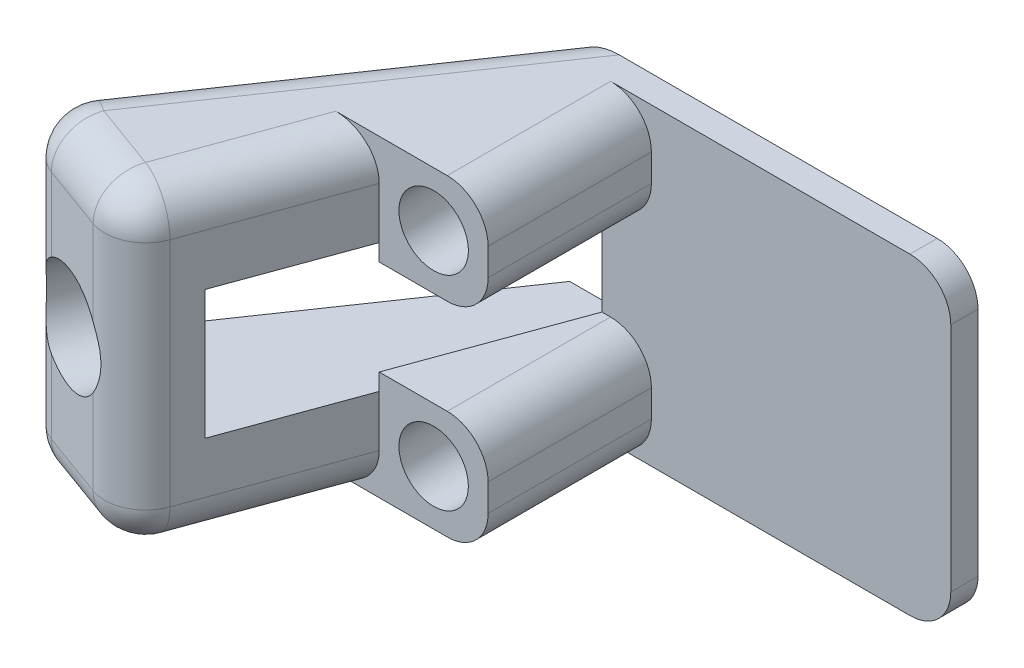
SolidWorks part; units mm, degrees
ref_plane "Alzado" through (0, 0, 0) normal (0, 0, 1) x (1, 0, 0)
ref_plane "Planta" through (0, 0, 0) normal (0, 1, 0) x (1, 0, 0)
ref_plane "Vista lateral" through (0, 0, 0) normal (1, 0, 0) x (0, 0, -1)
sketch "Croquis3" plane through (0, 0, 0) normal (0, 0, 1) x (1, 0, 0)
  line L0 (-63.169, 19.4366) -> (-33.169, 19.4366) construction
  line L1 (-63.169, 30.9366) -> (-33.169, 30.9366)
  line L2 (-63.169, 30.9366) -> (-63.169, 7.9366)
  line L3 (-63.169, 7.9366) -> (-33.169, 7.9366)
  line L4 (-33.169, 30.9366) -> (-33.169, 7.9366)
  circle A0 centre (-59.169, 26.9366) radius 2.55
  circle A1 centre (-59.169, 11.9366) radius 2.55
  dimension "D4" = 5.1
  dimension "D1" = 23
  dimension "D2" = 30
  dimension "D3" = 7.5
  dimension "D5" = 4
extrude "Saliente-Extruir2" add sketch "Croquis3" along normal blind 2
sketch "Croquis5" plane through (0, 0, 2) normal (0, 0, 1) x (1, 0, 0)
  line L0 (-63.169, 19.4366) -> (-33.169, 19.4366) construction
  line L1 (-63.169, 7.9366) -> (-55.169, 7.9366)
  line L2 (-63.169, 7.9366) -> (-63.169, 15.9366)
  line L3 (-63.169, 15.9366) -> (-55.169, 15.9366)
  line L4 (-55.169, 7.9366) -> (-55.169, 15.9366)
  line L5 (-63.169, 30.9366) -> (-63.169, 7.9366) construction
  line L6 (-33.169, 7.9366) -> (-33.169, 30.9366) construction
  line L7 (-55.169, 30.9366) -> (-55.169, 22.9366)
  line L8 (-63.169, 22.9366) -> (-55.169, 22.9366)
  line L9 (-63.169, 30.9366) -> (-63.169, 22.9366)
  line L10 (-63.169, 30.9366) -> (-55.169, 30.9366)
  circle A0 centre (-59.169, 11.9366) radius 2.55
  circle A1 centre (-59.169, 26.9366) radius 2.55
  circle A2 centre (-59.169, 11.9366) radius 2.55 construction
  dimension "D1" = 8
  dimension "D2" = 8
extrude "Saliente-Extruir3" add sketch "Croquis5" along normal blind 12
sketch "Croquis6" plane through (0, 30.9366, 0) normal (0, 1, 0) x (1, 0, 0)
  line L0 (-63.169, -14) -> (-68.2993, -28.0954)
  line L1 (-68.2993, -28.0954) -> (-79.5756, -23.9911)
  line L2 (-79.5756, -23.9911) -> (-63.169, 0)
  line L3 (-63.169, -14) -> (-63.169, -25.6252) construction
  line L4 (-63.169, -14) -> (-63.169, 0)
  dimension "D1" = 12
  dimension "D2" = 20
  dimension "D3" = 15
extrude "Saliente-Extruir4" add sketch "Croquis6" against normal up to vertex (23 mm away) up to point (-63.169, 7.9366, 14)
sketch "Croquis7" plane through (-17.0192, 0, 46.7598) normal (-0.342, 0, 0.9397) x (0.9397, 0, 0.342)
  circle A0 centre (-60.5712, 19.4366) radius 3.75
extrude "Cortar-Extruir1" cut sketch "Croquis7" against normal up to vertex (15 mm away) up to point (-63.169, 15.9366, 14)
sketch "Croquis13" plane through (-17.0192, 0, 46.7598) normal (-0.342, 0, 0.9397) x (0.9397, 0, 0.342)
  line L1 (-60.5712, 14.7023) -> (-56.4712, 17.0695)
  line L2 (-56.4712, 17.0695) -> (-56.4712, 21.8038)
  line L3 (-56.4712, 21.8038) -> (-60.5712, 24.1709)
  line L4 (-60.5712, 24.1709) -> (-64.6712, 21.8038)
  line L5 (-64.6712, 21.8038) -> (-64.6712, 17.0695)
  line L6 (-64.6712, 17.0695) -> (-60.5712, 14.7023)
  circle A0 centre (-60.5712, 19.4366) radius 4.1 construction
  dimension "D1" = 8.2
extrude "Cortar-Extruir7" cut sketch "Croquis13" against normal blind 20 from offset 3 offset against normal yes
sketch "Croquis14" plane through (-15.9931, 0, 43.9408) normal (0.342, 0, -0.9397) x (-0.9397, 0, -0.342)
  line L1 (64.6372, 24.1709) -> (56.5052, 24.1709)
  line L2 (64.6372, 24.1709) -> (64.6372, 14.7023)
  line L3 (64.6372, 14.7023) -> (56.5052, 14.7023)
  line L4 (56.5052, 24.1709) -> (56.5052, 14.7023)
  line L5 (64.6372, 24.1709) -> (56.5052, 14.7023) construction
  line L6 (64.6372, 14.7023) -> (56.5052, 24.1709) construction
  point P0 (60.5712, 19.4366)
extrude "Cortar-Extruir8" cut sketch "Croquis14" along normal blind 25 from offset 2
sketch "Croquis15" plane through (-53.0975, 0, -19.3259) normal (-0.9397, 0, -0.342) x (-0.342, 0, 0.9397)
  line L1 (44.7608, 24.1709) -> (20.5662, 24.1709)
  line L2 (44.7608, 24.1709) -> (44.7608, 14.7023)
  line L3 (44.7608, 14.7023) -> (20.5662, 14.7023)
  line L4 (20.5662, 24.1709) -> (20.5662, 14.7023)
extrude "Cortar-Extruir9" cut sketch "Croquis15" against normal up to vertex (1.934 mm away) up to point (-63.169, 15.9366, 14)
fillet "Redondeo1" radius 3 14 edges at (-33.169, 7.9366, 1) (-33.169, 30.9366, 1) (-55.169, 7.9366, 8) (-55.169, 15.9366, 8) (-55.169, 30.9366, 8) (-55.169, 22.9366, 8) (-73.9375, 7.9366, 26.0433) (-68.2993, 19.4366, 28.0954) (-73.9375, 30.9366, 26.0433) (-79.5756, 19.4366, 23.9911) (-71.3723, 7.9366, 11.9956) (-71.3723, 30.9366, 11.9956) (-65.7342, 7.9366, 21.0477) (-65.7342, 30.9366, 21.0477)
